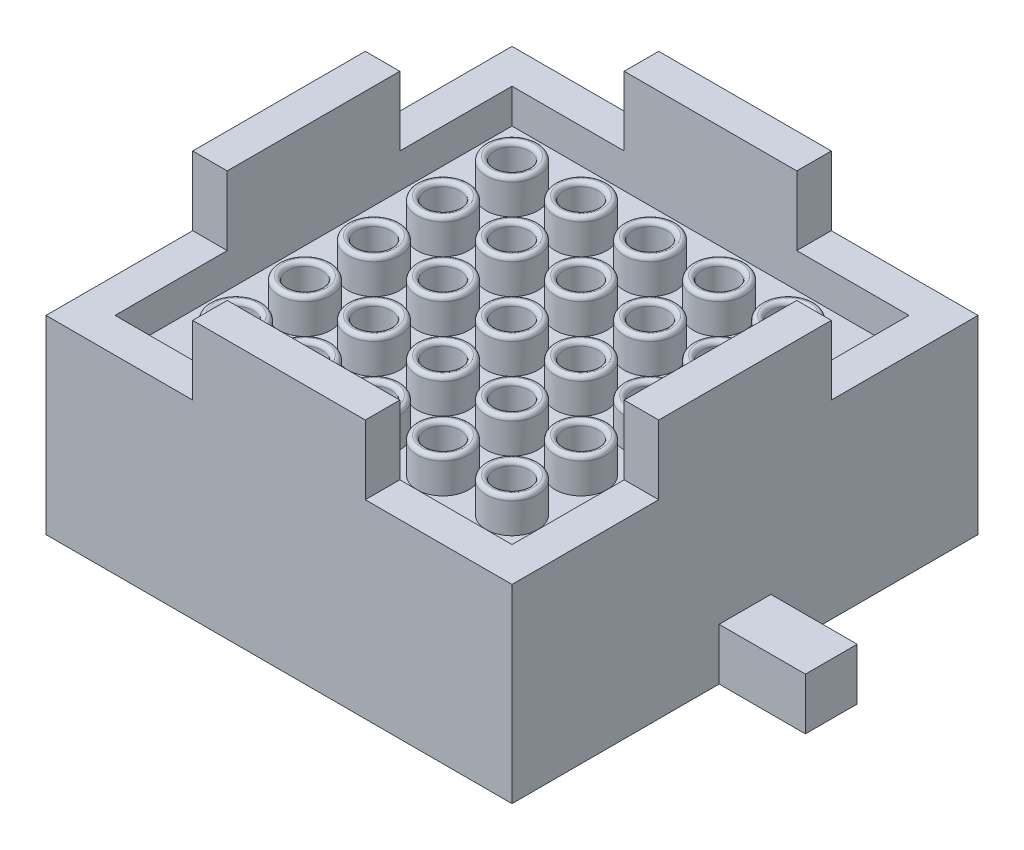
SolidWorks part; units mm, degrees
ref_plane "Front Plane" through (0, 0, 0) normal (0, 0, 1) x (1, 0, 0)
ref_plane "Top Plane" through (0, 0, 0) normal (0, 1, 0) x (1, 0, 0)
ref_plane "Right Plane" through (0, 0, 0) normal (1, 0, 0) x (0, 0, -1)
sketch "Sketch1" plane through (0, 0, 0) normal (0, 1, 0) x (1, 0, 0)
  line L0 (-13.5, 13.5) -> (13.5, 13.5)
  line L1 (-11.5, -11.5) -> (11.5, -11.5)
  line L2 (-11.5, -11.5) -> (-11.5, 11.5)
  line L3 (-11.5, 11.5) -> (11.5, 11.5)
  line L4 (11.5, -11.5) -> (11.5, 11.5)
  line L5 (-11.5, -11.5) -> (11.5, 11.5) construction
  line L6 (-11.5, 11.5) -> (11.5, -11.5) construction
  line L7 (13.5, -13.5) -> (13.5, 13.5)
  line L8 (-13.5, -13.5) -> (13.5, -13.5)
  line L9 (-13.5, -13.5) -> (-13.5, 13.5)
  point P0 (0, 0)
  dimension "D1" = 23
  dimension "D2" = 2
extrude "Boss-Extrude1" add sketch "Sketch1" along normal blind 2
sketch "Sketch2" plane through (0, 0, 0) normal (0, -1, 0) x (1, 0, 0)
  line L1 (-13.5, 13.5) -> (13.5, 13.5)
  line L2 (-13.5, 13.5) -> (-13.5, -13.5)
  line L3 (-13.5, -13.5) -> (13.5, -13.5)
  line L4 (13.5, 13.5) -> (13.5, -13.5)
  line L5 (-13.5, 13.5) -> (13.5, -13.5) construction
  line L6 (-13.5, -13.5) -> (13.5, 13.5) construction
  point P0 (0, 0)
extrude "Boss-Extrude2" add sketch "Sketch2" along normal blind 2
sketch "Sketch3" plane through (0, -2, 0) normal (0, -1, 0) x (1, 0, 0)
  line L0 (-11.5, 11.5) -> (11.5, 11.5)
  line L1 (-13.5, -13.5) -> (13.5, -13.5)
  line L2 (-13.5, -13.5) -> (-13.5, 13.5)
  line L3 (-13.5, 13.5) -> (13.5, 13.5)
  line L4 (13.5, -13.5) -> (13.5, 13.5)
  line L5 (-13.5, -13.5) -> (13.5, 13.5) construction
  line L6 (-13.5, 13.5) -> (13.5, -13.5) construction
  line L7 (11.5, -11.5) -> (11.5, 11.5)
  line L8 (-11.5, -11.5) -> (11.5, -11.5)
  line L9 (-11.5, -11.5) -> (-11.5, 11.5)
  point P0 (0, 0)
  dimension "D1" = 2
extrude "Boss-Extrude3" add sketch "Sketch3" along normal blind 5
sketch "Sketch6" plane through (0, 0, 0) normal (0, 1, 0) x (1, 0, 0)
  line L0 (11.5, -11.5) -> (11.5, 11.5) construction
  line L1 (11.5, 11.5) -> (-11.5, 11.5) construction
  circle A0 centre (8, 8) radius 1.5
  dimension "D2" = 3
  dimension "D1" = 3.5
  dimension "D3" = 3.5
extrude "Boss-Extrude5" add sketch "Sketch6" along normal blind 2
sketch "Sketch7" plane through (0, 2, 0) normal (0, 1, 0) x (1, 0, 0)
  circle A0 centre (8, 8) radius 1
  dimension "D1" = 2
extrude "Cut-Extrude2" cut sketch "Sketch7" against normal up to next
fillet "Fillet1" radius 0.25 2 edges at (8, 2, -6.5) (8, 2, -7)
pattern_linear "LPattern3" count 5 spacing 4 along (0, 0, 1) count 5 spacing 4 along (-1, 0, 0) of "Boss-Extrude5", "Cut-Extrude2", "Fillet1"
sketch "Sketch11" plane through (0, -2, 0) normal (0, -1, 0) x (1, 0, 0)
  line L0 (11.5, 11.5) -> (-11.5, 11.5) construction
  line L1 (-11.5, 11.5) -> (-11.5, -11.5) construction
  circle A0 centre (-9.9, 9.9) radius 0.75
  dimension "D1" = 1.5
  dimension "D3" = 1.6
  dimension "D2" = 1.6
extrude "Boss-Extrude8" add sketch "Sketch11" along normal up to surface (5 mm away) up to face at (0, -7, 0)
pattern_linear "LPattern2" count 6 spacing 4 along (1, 0, 0) count 6 spacing 4 along (0, 0, -1) of "Boss-Extrude8"
sketch "Sketch8" plane through (0, -7, 0) normal (0, -1, 0) x (1, 0, 0)
  line L1 (-13.5, -13.5) -> (13.5, -13.5)
  line L2 (-13.5, -13.5) -> (-13.5, 13.5)
  line L3 (-13.5, 13.5) -> (13.5, 13.5)
  line L4 (13.5, -13.5) -> (13.5, 13.5)
  line L5 (-13.5, -13.5) -> (13.5, 13.5) construction
  line L6 (-13.5, 13.5) -> (13.5, -13.5) construction
  point P0 (0, 0)
extrude "Boss-Extrude6" add sketch "Sketch8" along normal blind 2
sketch "Sketch9" plane through (0, -9, 0) normal (0, -1, 0) x (1, 0, 0)
  circle A0 centre (0, 0) radius 4.25
  dimension "D1" = 8.5
extrude "Cut-Extrude3" cut sketch "Sketch9" against normal blind 7
sketch "Sketch10" plane through (0, 2, 0) normal (0, 1, 0) x (1, 0, 0)
  line L0 (-13.5, 0) -> (-11.5, 0) construction
  line L1 (-13.5, 13.5) -> (-13.5, -13.5) construction
  line L2 (-11.5, 11.5) -> (-11.5, -11.5) construction
  line L4 (-11.5, 5) -> (-13.5, 5)
  line L5 (-11.5, 5) -> (-11.5, -5)
  line L6 (-11.5, -5) -> (-13.5, -5)
  line L7 (-13.5, 5) -> (-13.5, -5)
  line L8 (-11.5, 5) -> (-13.5, -5) construction
  line L9 (-11.5, -5) -> (-13.5, 5) construction
  point P6 (-12.5, 0)
  dimension "D1" = 10
extrude "Boss-Extrude7" add sketch "Sketch10" along normal blind 4
pattern_circular "CirPattern2" count 4 over 360 about axis through (0, -7.001, 0) along (0, 1, 0) of "Boss-Extrude7"
sketch "Sketch12" plane through (-13.5, 0, 0) normal (-1, 0, 0) x (0, 0, 1)
  line L0 (13.5, -9) -> (-13.5, -9) construction
  line L1 (1.5, -6) -> (-1.5, -6)
  line L2 (1.5, -6) -> (1.5, -9)
  line L3 (1.5, -9) -> (-1.5, -9)
  line L4 (-1.5, -6) -> (-1.5, -9)
  line L5 (1.5, -6) -> (-1.5, -9) construction
  line L6 (1.5, -9) -> (-1.5, -6) construction
  line L7 (0, 0) -> (0, -9) construction
  point P0 (0, -7.5)
  dimension "D1" = 3
extrude "Boss-Extrude9" add sketch "Sketch12" along normal blind 5
pattern_circular "CirPattern1" count 2 over 360 about axis through (0, -7.001, 0) along (0, 1, 0) of "Boss-Extrude9"
equation "\"D3@Sketch6\"=\"D1@Sketch6\""
equation "\"D3@Sketch11\"=\"D2@Sketch11\""
